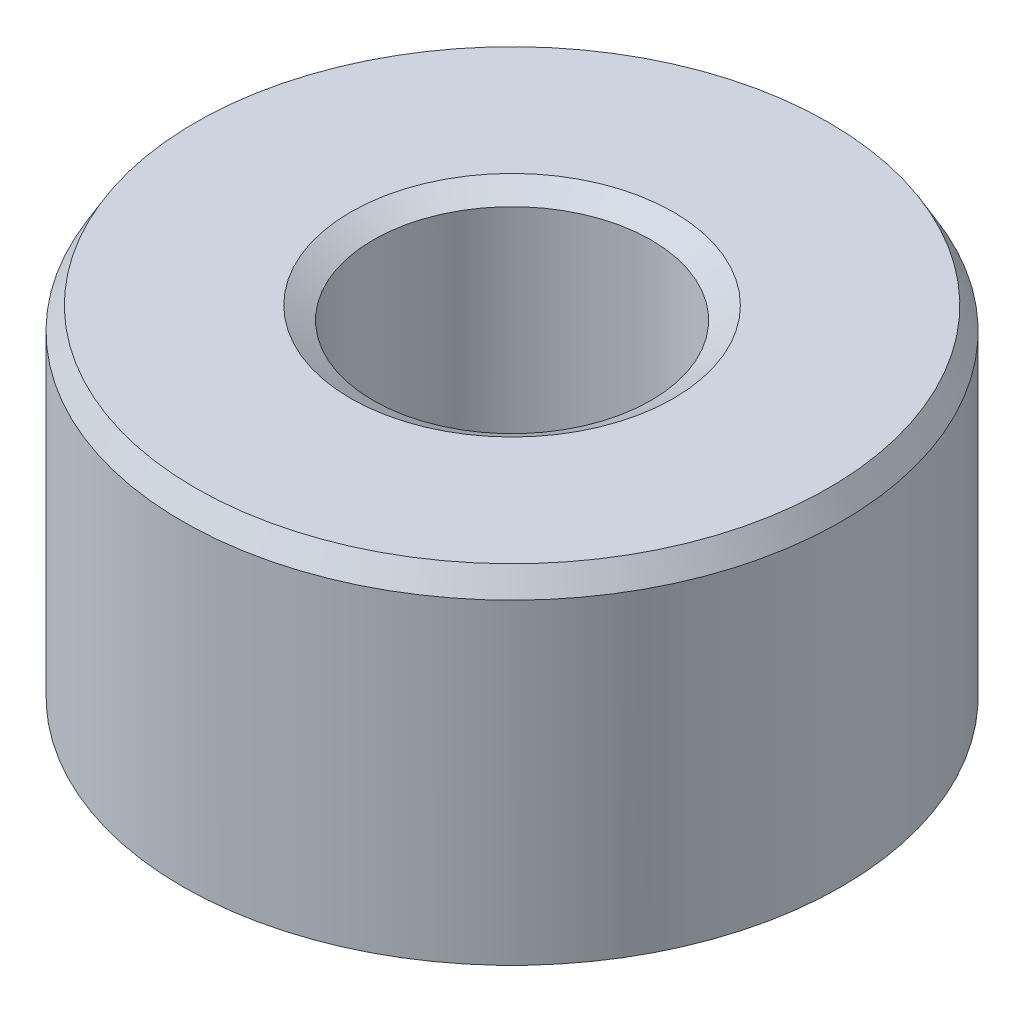
SolidWorks part; units mm, degrees
ref_plane "Front Plane" through (0, 0, 0) normal (0, 0, 1) x (1, 0, 0)
ref_plane "Top Plane" through (0, 0, 0) normal (0, 1, 0) x (1, 0, 0)
ref_plane "Right Plane" through (0, 0, 0) normal (1, 0, 0) x (0, 0, -1)
sketch "Sketch1" plane through (0, 0, 0) normal (0, 1, 0) x (1, 0, 0)
  circle A0 centre (0, 0) radius 57.5
  dimension "SLEEVE_OD" = 115
extrude "Boss-Extrude1" add sketch "Sketch1" along normal blind 61.3514
sketch "Sketch2" plane through (0, 0, 0) normal (0, 1, 0) x (1, 0, 0)
  circle A0 centre (0, 0) radius 24.2541
  dimension "BORE_D" = 48.5082
extrude "Cut-Extrude1" cut sketch "Sketch2" along normal through all
chamfer "Chamfer1" distance 3.9139 angle 30 4 edges at (0, 61.3514, 24.2541) (0, 0, 24.2541) (0, 0, 57.5) (0, 61.3514, 57.5) first distance on face at (0, 61.3514, 24.2541) first distance on face at (0, 0, 24.2541) first distance on face at (0, 61.3514, 57.5)
